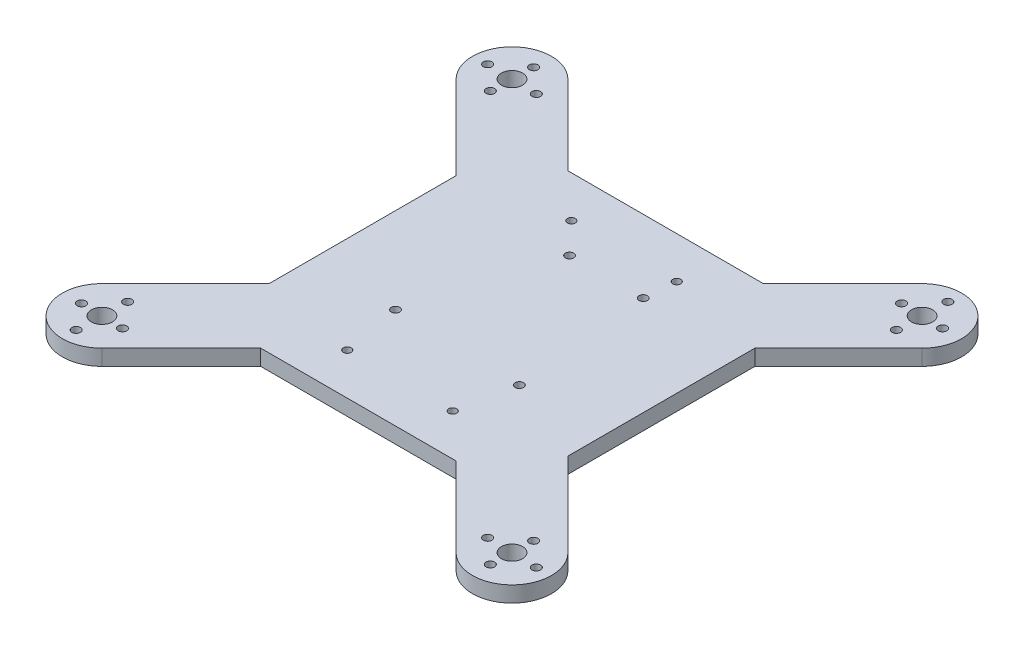
SolidWorks part; units mm, degrees
ref_plane "Front Plane" through (0, 0, 0) normal (0, 0, 1) x (1, 0, 0)
ref_plane "Top Plane" through (0, 0, 0) normal (0, 1, 0) x (1, 0, 0)
ref_plane "Right Plane" through (0, 0, 0) normal (1, 0, 0) x (0, 0, -1)
sketch "Sketch1" plane through (0, 0, 0) normal (0, 1, 0) x (1, 0, 0)
  line L0 (-67.1751, 88.3883) -> (88.3883, -67.1751)
  line L1 (-77.7817, 77.7817) -> (77.7817, 77.7817) construction
  line L2 (-77.7817, 77.7817) -> (-77.7817, -77.7817) construction
  line L3 (-77.7817, -77.7817) -> (77.7817, -77.7817) construction
  line L4 (77.7817, 77.7817) -> (77.7817, -77.7817) construction
  line L5 (-77.7817, 77.7817) -> (77.7817, -77.7817) construction
  line L6 (-77.7817, -77.7817) -> (77.7817, 77.7817) construction
  line L7 (67.1751, 88.3883) -> (-88.3883, -67.1751)
  line L8 (88.3883, 67.1751) -> (-67.1751, -88.3883)
  line L9 (-88.3883, 67.1751) -> (67.1751, -88.3883)
  line L10 (0, -1000) -> (0, 49000) construction
  line L11 (-1000, 0) -> (49000, 0) construction
  circle A0 centre (-77.7817, 77.7817) radius 15
  circle A1 centre (77.7817, 77.7817) radius 15
  circle A2 centre (-77.7817, -77.7817) radius 15
  circle A3 centre (77.7817, -77.7817) radius 15
  circle A4 centre (-77.7817, 77.7817) radius 4
  circle A5 centre (77.7817, 77.7817) radius 4
  circle A6 centre (77.7817, -77.7817) radius 4
  circle A7 centre (-77.7817, -77.7817) radius 4
  point P0 (0, 0)
  point P14 (10.6066, 10.6066)
  point P16 (10.6066, -10.6066)
  dimension "D4" = 8
  dimension "D1" = 220
  dimension "D2" = 30
  dimension "D3" = 30
extrude "Boss-Extrude1" add sketch "Sketch1" along normal blind 6 contours A0 A4 | A0 L9 L7 L0 | A2 A7 | L7 A2 L8 L9 | A3 L0 L8 L9 | L8 A1 L7 L0 | L7 L9 L8 L0 | A3 A6 | A1 A5 region at (-40.0766, 0, -40.0766) region at (-64.3155, 0, -83.3596) region at (40.0766, 0, -40.0766) region at (0, 0, 0) region at (40.0766, 0, 40.0766) region at (83.3596, 0, -91.248) region at (-40.0766, 0, 40.0766) region at (91.248, 0, 72.2039) region at (-72.2039, 0, 64.3155)
sketch "Sketch5" plane through (0, 6, 0) normal (0, 1, 0) x (1, 0, 0)
  line L0 (26.67, -35.3069) -> (-26.67, -35.3069)
  line L1 (26.67, -35.3069) -> (26.67, 30.7331)
  line L2 (21.59, 33.2731) -> (-11.176, 33.2731)
  line L3 (-26.67, -35.3069) -> (-26.67, 30.7331)
  line L4 (-26.67, 30.7331) -> (-13.716, 30.7331)
  line L5 (-13.716, 30.7331) -> (-11.176, 33.2731)
  line L6 (21.59, 33.2731) -> (24.13, 30.7331)
  line L7 (24.13, 30.7331) -> (26.67, 30.7331)
  line L8 (0, -1000) -> (0, 49000) construction
  line L10 (-1000, 0) -> (49000, 0) construction
  circle A0 centre (19.05, 30.7331) radius 1.5875
  circle A1 centre (-8.89, 30.7331) radius 1.5875
  circle A2 centre (24.13, -21.3369) radius 1.5875
  circle A3 centre (-24.13, -20.0669) radius 1.5875
  point P20 (0, -35.3069)
  line M10 (0, 21.2132) -> (-67.1751, 88.3883)
  line M12 (-88.3883, 67.1751) -> (-21.2132, 0)
  line M13 (-21.2132, 0) -> (-88.3883, -67.1751)
  line M15 (-67.1751, -88.3883) -> (0, -21.2132)
  line M16 (0, -21.2132) -> (67.1751, -88.3883)
  line M18 (88.3883, -67.1751) -> (21.2132, 0)
  line M19 (21.2132, 0) -> (88.3883, 67.1751)
  line M21 (67.1751, 88.3883) -> (0, 21.2132)
  dimension "D5" = 3.175
  dimension "D1" = 2.54
  dimension "D2" = 45
  dimension "D3" = 40.386
  dimension "D4" = 45
  dimension "D6" = 35.56
  dimension "D7" = 7.62
  dimension "D8" = 2.54
  dimension "D9" = 50.8
  dimension "D10" = 13.97
  dimension "D11" = 15.24
  dimension "D12" = 53.34
  dimension "D13" = 66.04
  dimension "D14" = 3.5921
  dimension "D15" = 2.54
  dimension "D16" = 2.54
  dimension "D17" = 2.54
  dimension "D18" = 32.766
  dimension "D19" = 66.04
  dimension "D20" = 12.954
extrude "Boss-Extrude2" add sketch "Sketch5" against normal blind 6 contours A1 M10 | A1 L5 L4 L3 L0 L1 L7 L6 L2 A3 A2 A0 M10 M12 M13 M15 M16 M18 M19 M21 | L3 M13 M12 | L1 M18 M19 | L0 M16 M15 | A1 L2 L5 M10 M21 region at (0.1063, 6, 1.0525) region at (0, 6, 30.609) region at (24.8511, 6, 0) region at (-24.8511, 6, 0) region at (0.3445, 6, -29.1791) region at (-8.5785, 6, -31.0446)
extrude "Cut-Extrude1" cut sketch "Sketch5<3>" against normal through all contours A1 | A0 | A2 | A3
sketch "Sketch5<3>" plane through (0, 6, 0) normal (0, 1, 0) x (1, 0, 0) same geometry as "Sketch5"
sketch "Sketch6" plane through (0, 6, 0) normal (0, 1, 0) x (1, 0, 0)
  line L0 (-1000, 0) -> (49000, 0) construction
  line L1 (0, -1000) -> (0, 49000) construction
  line L2 (0, 0) -> (-35355.3391, 35355.3391) construction
  line L3 (0, 0) -> (35355.3391, 35355.3391) construction
  line L4 (-77.5182, -68.2854) -> (-78.0453, -87.2781) construction
  line L5 (-69.7848, -78.0037) -> (-85.7787, -77.5598) construction
  circle A4 centre (-69.7848, -78.0037) radius 1.625
  circle A5 centre (-78.0453, -87.2781) radius 1.625
  circle A6 centre (-77.5182, -68.2854) radius 1.625
  circle A7 centre (-85.7787, -77.5598) radius 1.625
  circle A28 centre (-77.7817, -77.7817) radius 4 construction
  circle A29 centre (-77.7817, -77.7817) radius 4
  circle A30 centre (68.2854, -77.5182) radius 1.625
  circle A31 centre (87.2781, -78.0453) radius 1.625
  circle A32 centre (78.0037, -69.7848) radius 1.625
  circle A33 centre (77.5598, -85.7787) radius 1.625
  circle A38 centre (-87.2781, 78.0453) radius 1.625
  circle A39 centre (-77.5598, 85.7787) radius 1.625
  circle A40 centre (-78.0037, 69.7848) radius 1.625
  circle A41 centre (-68.2854, 77.5182) radius 1.625
  circle A42 centre (78.0453, 87.2781) radius 1.625
  circle A43 centre (77.5182, 68.2854) radius 1.625
  circle A44 centre (85.7787, 77.5598) radius 1.625
  circle A45 centre (69.7848, 78.0037) radius 1.625
  point P1 (0, 0)
  point P45 (0, 0)
  dimension "D1" = 18.9927
  dimension "D2" = 15.9938
  dimension "D3" = 9.7183
  dimension "D4" = 12.4197
  dimension "D5" = 12.4197
  dimension "D6" = 12.4197
extrude "Cut-Extrude2" cut sketch "Sketch6" against normal up to next (6 mm away)
sketch "Sketch7" plane through (0, 6, 0) normal (0, 1, 0) x (1, 0, 0)
  line L0 (88.3883, 67.1751) -> (26.67, 5.4568) construction
  line L1 (26.67, -5.4568) -> (26.67, 5.4568) construction
  line L2 (26.67, -5.4568) -> (88.3883, -67.1751) construction
  line L3 (-26.67, -5.4568) -> (-88.3883, -67.1751) construction
  line L4 (-88.3883, 67.1751) -> (-26.67, 5.4568) construction
  line L5 (-26.67, -5.4568) -> (-26.67, 5.4568) construction
  line L6 (88.3883, 67.1751) -> (26.67, 5.4568)
  line L7 (26.67, -5.4568) -> (26.67, 5.4568)
  line L8 (26.67, -5.4568) -> (88.3883, -67.1751)
  line L9 (-26.67, -5.4568) -> (-88.3883, -67.1751)
  line L10 (-88.3883, 67.1751) -> (-26.67, 5.4568)
  line L11 (-26.67, -5.4568) -> (-26.67, 5.4568)
  line L12 (-56.67, 35.4568) -> (-56.67, -35.4568)
  line L13 (0, -1000) -> (0, 49000) construction
  line L14 (56.67, 35.4568) -> (56.67, -35.4568)
  line L15 (-11.6179, 32.8311) -> (-11.176, 33.2731) construction
  line L16 (67.1751, 88.3883) -> (12.0599, 33.2731) construction
  line L17 (12.0599, 33.2731) -> (-11.176, 33.2731) construction
  line L18 (-67.1751, 88.3883) -> (-11.6179, 32.8311) construction
  line L19 (-11.6179, 32.8311) -> (-11.176, 33.2731)
  line L20 (67.1751, 88.3883) -> (12.0599, 33.2731)
  line L21 (12.0599, 33.2731) -> (-11.176, 33.2731)
  line L22 (-67.1751, 88.3883) -> (-11.6179, 32.8311)
  line L23 (14.0937, -35.3069) -> (67.1751, -88.3883) construction
  line L24 (14.0937, -35.3069) -> (-14.0937, -35.3069) construction
  line L25 (-14.0937, -35.3069) -> (-67.1751, -88.3883) construction
  line L26 (14.0937, -35.3069) -> (67.1751, -88.3883)
  line L27 (14.0937, -35.3069) -> (-14.0937, -35.3069)
  line L28 (-14.0937, -35.3069) -> (-67.1751, -88.3883)
  line L29 (-1000, 0) -> (49000, 0) construction
  line L30 (-37.0599, 58.2731) -> (37.0599, 58.2731)
  line L31 (-37.0599, -58.2731) -> (37.0599, -58.2731)
  point P17 (0, 0)
  point P28 (0, 0)
  point P30 (0, 0)
  line M25 (-14.0937, -35.3069) -> (14.0937, -35.3069)
  line M26 (14.0937, -35.3069) -> (67.1751, -88.3883)
  line M29 (26.67, -5.4568) -> (26.67, 5.4568)
  line M30 (26.67, 5.4568) -> (88.3883, 67.1751)
  line M33 (12.0599, 33.2731) -> (-11.176, 33.2731)
  line M34 (-11.176, 33.2731) -> (-11.6179, 32.8311)
  line M35 (-11.6179, 32.8311) -> (-67.1751, 88.3883)
  line M38 (-26.67, 5.4568) -> (-26.67, -5.4568)
  line M39 (-26.67, -5.4568) -> (-88.3883, -67.1751)
  dimension "D1" = 30
  dimension "D2" = 25
extrude "Boss-Extrude3" add sketch "Sketch7" against normal blind 6 contours L14 L8 M30 M29 | L10 L12 M39 M38 | L28 L31 M26 M25 | L30 L20 M35 M34 M33 region at (45.3363, 6, 0) region at (-45.3363, 6, 0) region at (-0.0018, 6, -47.8914) region at (0, 6, 48.5085)
sketch "Sketch8" plane through (0, 6, 0) normal (0, 1, 0) x (1, 0, 0)
  line L0 (0, -1000) -> (0, 49000) construction
  line L1 (-1000, 0) -> (49000, 0) construction
  line L2 (-20, 42.5) -> (20, 42.5) construction
  line L3 (-20, -42.5) -> (-20, 42.5) construction
  line L4 (-20, -42.5) -> (20, -42.5) construction
  line L5 (20, 42.5) -> (20, -42.5) construction
  circle A0 centre (-20, 42.5) radius 1.5
  circle A1 centre (20, 42.5) radius 1.5
  circle A2 centre (20, -42.5) radius 1.5
  circle A3 centre (-20, -42.5) radius 1.5
  point P13 (0, 0)
  point P14 (0, 0)
  point P15 (0, 0)
  dimension "D3" = 3
  dimension "D4" = 3
  dimension "D5" = 3
  dimension "D6" = 3
  dimension "D1" = 40
  dimension "D2" = 85
extrude "Cut-Extrude7" cut sketch "Sketch8" along normal blind 6 and the other way through all
equation "\"Frame_Size\" = 220"
equation "\"Arm_Width\" = 30"
equation "\"Motor_Mount_Hole_Diameter\" = 8"
equation "\"Motor_Shaft_Diameter\" = 3"
equation "\"D1@Sketch1\"=\"Frame_Size\""
equation "\"D2@Sketch1\"=\"Arm_Width\""
equation "\"D3@Sketch1\"=\"Arm_Width\""
equation "\"D4@Sketch1\"=\"Motor_Mount_Hole_Diameter\""
equation "\"Frame_Thickness\" = 6"
equation "\"D1@Boss-Extrude1\"=\"Frame_Thickness\""
equation "\"D1@Boss-Extrude2\"=\"Frame_Thickness\""
equation "\"D1@Boss-Extrude3\"=\"Frame_Thickness\""
equation "\"Screw_Nut_Diameter\" = 5"
equation "\"Screw_Diameter\" = 3"
equation "\"Screw_Shaft_Length\" = 10"
equation "\"Screw_Hole_Separation_C2C\" = 20"
equation "\"Solder_Board_Small_Screw_Hole_Separation\" = 37"
equation "\"Solder_Board_Small_Screw_Hole_Diameter\" = 3.3"
equation "\"Solder_Board_Small_Length\" = 45.72"
equation "\"Solder_Board_Small_Width\" = 33.02"
equation "\"Solder_Board_Small_Thickness\" = 1.6"
equation "\"ESC_Length\" = 35"
equation "\"ESC_Width\" = 17"
equation "\"ESC_Thickness\" = 5"
equation "\"Battery_Length\" = 105"
equation "\"Battery_Width\" = 33"
equation "\"Battery_Thickness\" = 24"
equation "\"Battery_Holder_Screw_Hole_Distance_Long\" = 85"
equation "\"Battery_Holder_Screw_Hole_Distance_Short\" = 40"
equation "\"D1@Sketch8\"=\"Battery_Holder_Screw_Hole_Distance_Short\""
equation "\"D2@Sketch8\"=\"Battery_Holder_Screw_Hole_Distance_Long\""
equation "\"D3@Sketch8\"=\"Screw_Diameter\""
equation "\"D4@Sketch8\"=\"Screw_Diameter\""
equation "\"D5@Sketch8\"=\"Screw_Diameter\""
equation "\"D6@Sketch8\"=\"Screw_Diameter\""
